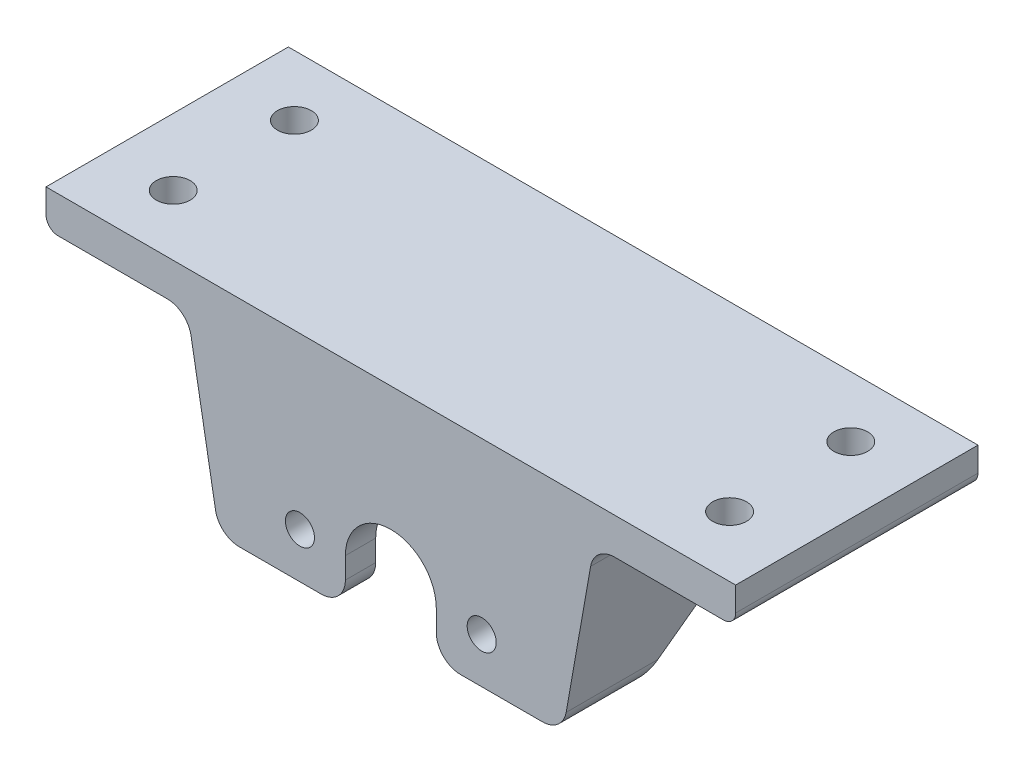
SolidWorks part; units mm, degrees
ref_plane "Front Plane" through (0, 0, 0) normal (0, 0, 1) x (1, 0, 0)
ref_plane "Top Plane" through (0, 0, 0) normal (0, 1, 0) x (1, 0, 0)
ref_plane "Right Plane" through (0, 0, 0) normal (1, 0, 0) x (0, 0, -1)
sketch "Motor Profile" plane through (0, 0, 0) normal (0, 0, 1) x (1, 0, 0)
  circle A0 centre (0, 0) radius 10 construction
  circle A1 centre (-7.5, 0) radius 1 construction
  circle A2 centre (7.5, 0) radius 1 construction
  circle A3 centre (0, 0) radius 3.5 construction
  point P8 (0, 0)
  point P9 (0, 0)
  point P15 (0, 0)
  point P16 (0, 0)
  point P20 (0, 0)
  point P27 (16.666, 7.7884)
  point P28 (0, 0)
  point P33 (13.9836, 7.6217)
  point P34 (0, 0)
  dimension "D1" = 7
  dimension "D2" = 2
  dimension "D3" = 20
  dimension "D4" = 2
  dimension "D5" = 15
  dimension "D6" = 7.5
sketch "Sketch2" plane through (0, 0, 0) normal (0, 0, 1) x (1, 0, 0)
  line L0 (-3.75, 0) -> (-3.75, -1.75)
  line L1 (3.75, 0) -> (3.75, -1.75)
  line L2 (-5.75, -3.75) -> (-12.5, -3.75)
  line L3 (-14.4696, -2.0973) -> (-16.4876, 9.3473)
  line L4 (5.75, -3.75) -> (12.5, -3.75)
  line L5 (14.4696, -2.0973) -> (16.4876, 9.3473)
  line L7 (-18.4572, 11) -> (-27.4572, 11)
  line L8 (18.4572, 11) -> (27.4572, 11)
  line L9 (-28.4572, 12) -> (-28.4572, 14)
  line L10 (-28.4572, 14) -> (28.4572, 14)
  line L11 (28.4572, 14) -> (28.4572, 12)
  arc A0 (3.75, 0) -> (-3.75, 0) centre (0, 0) ccw
  circle A1 centre (-7.5, 0) radius 1.2
  circle A2 centre (7.5, 0) radius 1.2
  arc A3 (-5.75, -3.75) -> (-3.75, -1.75) centre (-5.75, -1.75) ccw
  arc A4 (5.75, -3.75) -> (3.75, -1.75) centre (5.75, -1.75) cw
  arc A5 (-12.5, -3.75) -> (-14.4696, -2.0973) centre (-12.5, -1.75) cw
  arc A6 (14.4696, -2.0973) -> (12.5, -3.75) centre (12.5, -1.75) cw
  arc A8 (-16.4876, 9.3473) -> (-18.4572, 11) centre (-18.4572, 9) ccw
  arc A9 (16.4876, 9.3473) -> (18.4572, 11) centre (18.4572, 9) cw
  arc A10 (-27.4572, 11) -> (-28.4572, 12) centre (-27.4572, 12) cw
  arc A11 (28.4572, 12) -> (27.4572, 11) centre (27.4572, 12) cw
  point P20 (-3.75, -3.75)
  point P23 (3.75, -3.75)
  point P27 (-14.1782, -3.75)
  point P33 (-16.779, 11)
  point P36 (16.779, 11)
  point P39 (-28.4572, 11)
  dimension "D1" = 7.5
  dimension "D2" = 2.4
  dimension "D7" = 2
  dimension "D8" = 2
  dimension "D9" = 2
  dimension "D10" = 2
  dimension "D13" = 2
  dimension "D14" = 2
  dimension "D16" = 1
  dimension "D17" = 1
  dimension "D4" = 3.75
  dimension "D3" = 80
  dimension "D5" = 80
  dimension "D6" = 5
  dimension "D11" = 11
  dimension "D12" = 3
  dimension "D15" = 10
extrude "Boss-Extrude1" add sketch "Sketch2" against normal blind 2.5
ref_plane "Plane2" through (0, 0, -20) normal (0, 0, 1) x (1, 0, 0)
sketch "Sketch3" plane through (0, 0, -2.5) normal (0, 0, -1) x (-1, 0, 0)
  line L11 (-11, -2.75) -> (-11, 6)
  line L12 (-5.75, -3.75) -> (-12.5, -3.75) construction
  line L13 (-6, 11) -> (6, 11)
  line L14 (11, 6) -> (11, -2.75)
  line L15 (12.5, -3.75) -> (5.75, -3.75) construction
  line L16 (12, -3.75) -> (12.5, -3.75)
  line L17 (-12, -3.75) -> (-12.5, -3.75)
  line L22 (3.75, 0) -> (3.75, -1.75)
  line L23 (5.75, -3.75) -> (12.5, -3.75)
  line L24 (14.4696, -2.0973) -> (16.4876, 9.3473)
  line L25 (18.4572, 11) -> (27.4572, 11)
  line L26 (28.4572, 12) -> (28.4572, 14)
  line L27 (28.4572, 14) -> (-28.4572, 14)
  line L28 (-28.4572, 14) -> (-28.4572, 12)
  line L29 (-27.4572, 11) -> (-18.4572, 11)
  line L30 (-16.4876, 9.3473) -> (-14.4696, -2.0973)
  line L31 (-12.5, -3.75) -> (-5.75, -3.75)
  line L32 (-3.75, -1.75) -> (-3.75, 0)
  line L35 (14.4696, -2.0973) -> (16.4876, 9.3473)
  line L36 (18.4572, 11) -> (27.4572, 11)
  line L37 (28.4572, 12) -> (28.4572, 14)
  line L38 (28.4572, 14) -> (-28.4572, 14)
  line L39 (-28.4572, 14) -> (-28.4572, 12)
  line L40 (-27.4572, 11) -> (-18.4572, 11)
  line L41 (-16.4876, 9.3473) -> (-14.4696, -2.0973)
  arc A9 (-11, 6) -> (-6, 11) centre (-6, 6) cw
  arc A10 (11, 6) -> (6, 11) centre (6, 6) ccw
  arc A11 (-11, -2.75) -> (-12, -3.75) centre (-12, -2.75) cw
  arc A12 (12, -3.75) -> (11, -2.75) centre (12, -2.75) cw
  arc A18 (3.75, 0) -> (-3.75, 0) centre (0, 0) ccw
  arc A19 (3.75, -1.75) -> (5.75, -3.75) centre (5.75, -1.75) ccw
  arc A20 (12.5, -3.75) -> (14.4696, -2.0973) centre (12.5, -1.75) ccw
  arc A21 (18.4572, 11) -> (16.4876, 9.3473) centre (18.4572, 9) ccw
  arc A22 (27.4572, 11) -> (28.4572, 12) centre (27.4572, 12) ccw
  arc A23 (-28.4572, 12) -> (-27.4572, 11) centre (-27.4572, 12) ccw
  arc A24 (-16.4876, 9.3473) -> (-18.4572, 11) centre (-18.4572, 9) ccw
  arc A25 (-14.4696, -2.0973) -> (-12.5, -3.75) centre (-12.5, -1.75) ccw
  arc A26 (-5.75, -3.75) -> (-3.75, -1.75) centre (-5.75, -1.75) ccw
  arc A29 (12.5, -3.75) -> (14.4696, -2.0973) centre (12.5, -1.75) ccw
  arc A30 (18.4572, 11) -> (16.4876, 9.3473) centre (18.4572, 9) ccw
  arc A31 (27.4572, 11) -> (28.4572, 12) centre (27.4572, 12) ccw
  arc A32 (-28.4572, 12) -> (-27.4572, 11) centre (-27.4572, 12) ccw
  arc A33 (-16.4876, 9.3473) -> (-18.4572, 11) centre (-18.4572, 9) ccw
  arc A34 (-14.4696, -2.0973) -> (-12.5, -3.75) centre (-12.5, -1.75) ccw
  point P7 (0, 11)
  point P15 (10.2822, 11)
  point P26 (-11, -3.75)
  point P29 (11, -3.75)
  dimension "D3" = 5
  dimension "D4" = 5
  dimension "D5" = 1
  dimension "D6" = 1
  dimension "D2" = 11
  dimension "D1" = 0
extrude "Boss-Extrude2" add sketch "Sketch3" along direction (0, 0, 1) on the side of the normal up to surface (17.5 mm away) up to plane "Plane2"
sketch "Sketch6" plane through (0, 0, 0) normal (1, 0, 0) x (0, 0, -1)
  line L0 (6, -3.75) -> (20, 11)
  line L1 (20, -3.75) -> (0, -3.75) construction
  line L2 (20, 9.7625) -> (20, -9.7625) construction
  line L3 (20, 11) -> (0, 11) construction
  line L4 (6, -3.75) -> (20, -3.75)
  line L5 (20, -3.75) -> (20, 11)
  dimension "D1" = 6
extrude "Cut-Extrude1" cut sketch "Sketch6" against normal through all both and the other way through all
sketch "Sketch9" plane through (0, 11, 0) normal (0, -1, 0) x (1, 0, 0)
  line L0 (18.4572, -20) -> (27.4572, -20) construction
  line L3 (18.4572, 0) -> (27.4572, 0) construction
  circle A0 centre (22.9572, -15) radius 1.4
  circle A1 centre (22.9572, -5) radius 1.4
  point P2 (0, 0)
  point P5 (22.9572, -20)
  point P9 (22.9572, -6.3213)
  dimension "D1" = 2.8
  dimension "D2" = 5
  dimension "D3" = 5
extrude "Cut-Extrude2" cut sketch "Sketch9" against normal through all
mirror "Mirror1" about plane through (0, 0, 0) normal (1, 0, 0) of "Cut-Extrude2"
equation "\"D6@Motor Profile\" = \"D5@Motor Profile\" / 2"
equation "\"D5@Sketch2\"=\"D3@Sketch2\""
